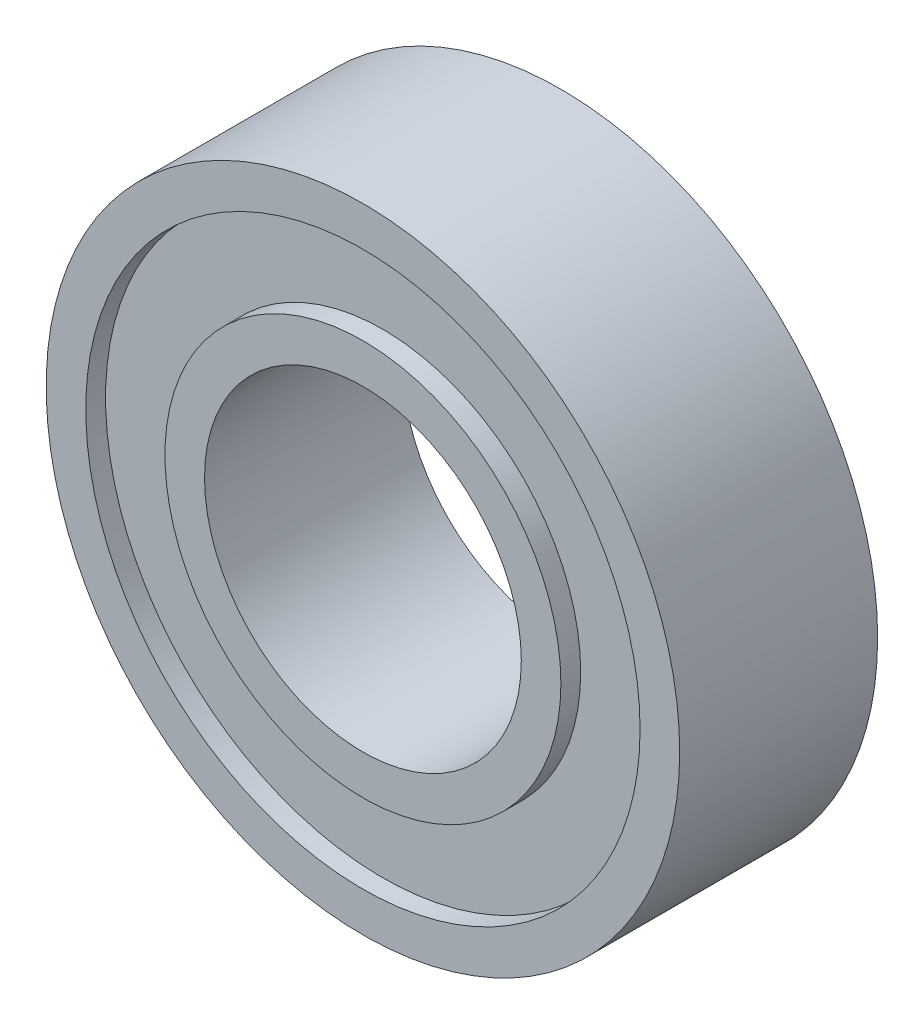
SolidWorks part; units mm, degrees
ref_plane "Plan de face" through (0, 0, 0) normal (0, 0, 1) x (1, 0, 0)
ref_plane "Plan de dessus" through (0, 0, 0) normal (0, 1, 0) x (1, 0, 0)
ref_plane "Plan de droite" through (0, 0, 0) normal (1, 0, 0) x (0, 0, -1)
sketch "Esquisse1" plane through (0, 0, 0) normal (0, 0, 1) x (1, 0, 0)
  circle A0 centre (0, 0) radius 8
  circle A1 centre (0, 0) radius 7
  circle A2 centre (0, 0) radius 5
  circle A3 centre (0, 0) radius 4
  dimension "D1" = 16
extrude "Boss.-Extru.1" add sketch "Esquisse1" along normal blind 5 contours A0 A1 region at (-7.7737, 0, 0)
extrude "Boss.-Extru.2" add sketch "Esquisse1<3>" along normal blind 4.5 contours A1 A2 region at (-6.802, 0, 0)
sketch "Esquisse1<3>" plane through (0, 0, 0) normal (0, 0, 1) x (1, 0, 0) same geometry as "Esquisse1"
extrude "Boss.-Extru.3" add sketch "Esquisse1<4>" along normal blind 5 contours A2 A3 region at (-4.8586, 0, 0)
sketch "Esquisse1<4>" plane through (0, 0, 0) normal (0, 0, 1) x (1, 0, 0) same geometry as "Esquisse1"
sketch "Esquisse2" plane through (0, 0, 0) normal (0, 0, -1) x (-1, 0, 0)
  circle A0 centre (0, 0) radius 7
  circle A1 centre (0, 0) radius 5
extrude "Enlèv. mat.-Extru.2" cut sketch "Esquisse2" against normal blind 0.5
